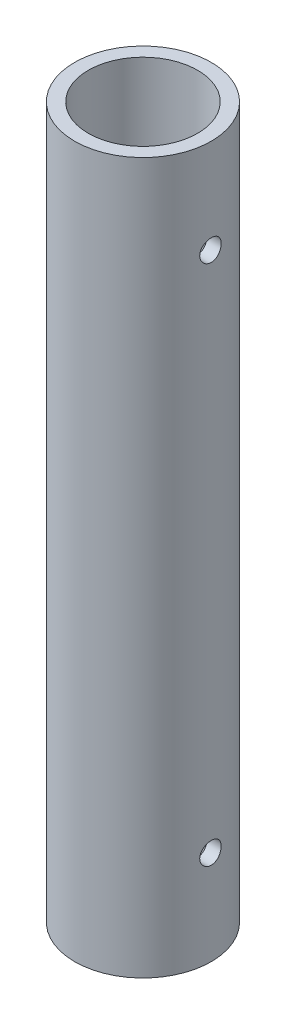
SolidWorks part; units mm, degrees
ref_plane "Front Plane" through (0, 0, 0) normal (0, 0, 1) x (1, 0, 0)
ref_plane "Top Plane" through (0, 0, 0) normal (0, 1, 0) x (1, 0, 0)
ref_plane "Right Plane" through (0, 0, 0) normal (1, 0, 0) x (0, 0, -1)
sketch "Sketch1" plane through (0, 0, 0) normal (0, 1, 0) x (1, 0, 0)
  circle A0 centre (0, 0) radius 15.875
  circle A1 centre (0, 0) radius 12.7
  dimension "D1" = 31.75
  dimension "D2" = 3.175
extrude "Boss-Extrude1" add sketch "Sketch1" along normal mid plane 165.1
sketch "Sketch2" plane through (0, 0, 0) normal (1, 0, 0) x (0, 0, -1)
  line L0 (15.875, 82.55) -> (-15.875, 82.55) construction
  circle A0 centre (0, 60.6425) radius 2.4892
  dimension "D1" = 4.9784
  dimension "D2" = 21.9075
extrude "Cut-Extrude1" cut sketch "Sketch2" against normal through all both and the other way through all
mirror "Mirror1" about plane through (0, 0, 0) normal (0, 1, 0) of "Cut-Extrude1"
